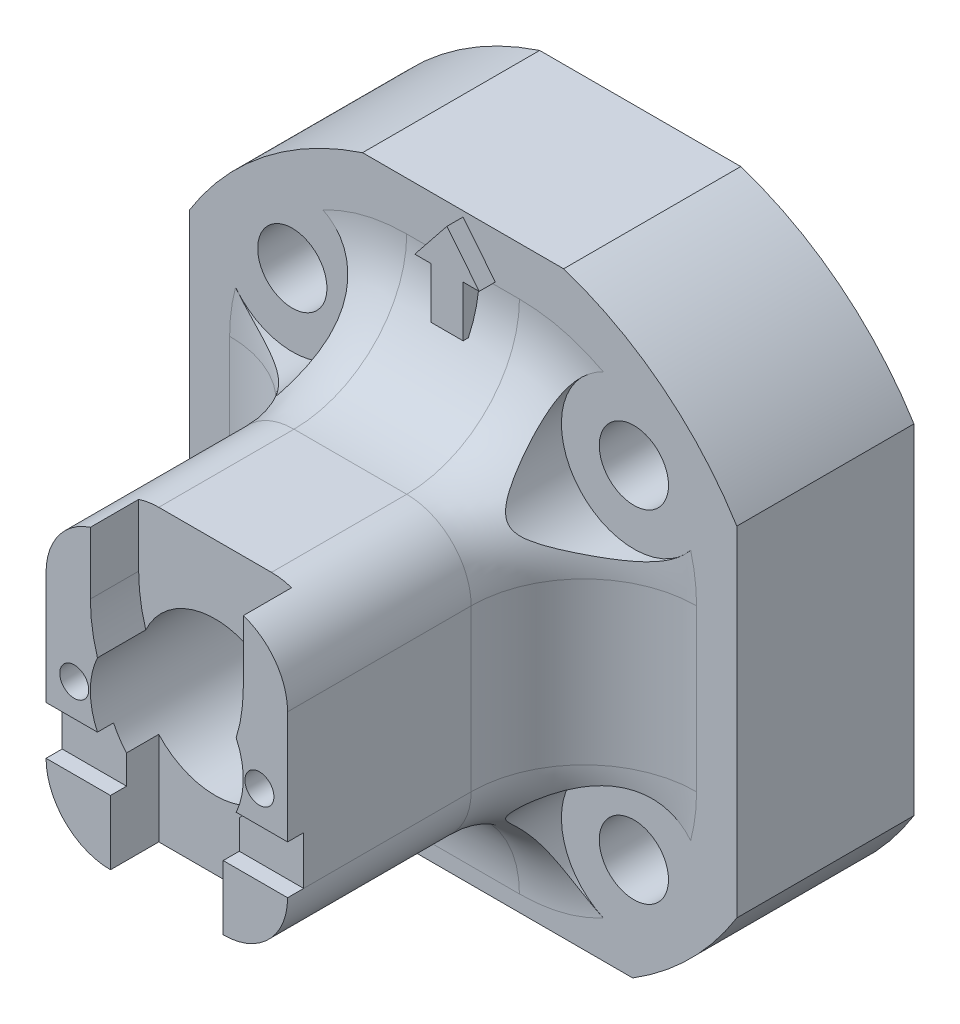
SolidWorks part; units mm, degrees
ref_plane "Front Plane" through (0, 0, 0) normal (0, 0, 1) x (1, 0, 0)
ref_plane "Top Plane" through (0, 0, 0) normal (0, 1, 0) x (1, 0, 0)
ref_plane "Right Plane" through (0, 0, 0) normal (1, 0, 0) x (0, 0, -1)
sketch "Sketch1" plane through (0, 0, 0) normal (0, 0, 1) x (1, 0, 0)
  circle A0 centre (0, 0) radius 20
  circle A1 centre (0, 0) radius 4.75
  dimension "D1" = 9.5
  dimension "D2" = 40
extrude "Boss-Extrude1" add sketch "Sketch1" along normal blind 11
sketch "Sketch2" plane through (0, 0, 11) normal (0, 0, 1) x (1, 0, 0)
  line L0 (0, 0) -> (0, 19) construction
  line L1 (-6.5933, 20) -> (6.5933, 20)
  line L2 (-6.5933, 20) -> (-6.5933, 19)
  line L3 (-6.5933, 19) -> (6.5933, 19)
  line L4 (6.5933, 20) -> (6.5933, 19)
  line L6 (-20, 15.8908) -> (-17, 15.8908)
  line L7 (-20, 15.8908) -> (-20, -10.5357)
  line L8 (-20, -10.5357) -> (-17, -10.5357)
  line L9 (-17, 15.8908) -> (-17, -10.5357)
  line L10 (20, 11.7256) -> (17, 11.7256)
  line L11 (20, 11.7256) -> (20, -14.8962)
  line L12 (20, -14.8962) -> (17, -14.8962)
  line L13 (17, 11.7256) -> (17, -14.8962)
  line L14 (19.7919, -20) -> (-18.9444, -20)
  line L15 (19.7919, -20) -> (19.7919, -17)
  line L16 (19.7919, -17) -> (-18.9444, -17)
  line L17 (-18.9444, -20) -> (-18.9444, -17)
  circle A0 centre (0, 0) radius 20 construction
  dimension "D1" = 1
  dimension "D2" = 3
extrude "Cut-Extrude1" cut sketch "Sketch2" against normal through all
sketch "Sketch3" plane through (0, 0, 11) normal (0, 0, 1) x (1, 0, 0)
  circle A0 centre (10.6066, -10.6066) radius 2 construction
  circle A1 centre (10.6066, 10.6066) radius 2 construction
  circle A2 centre (-10.6066, -10.6066) radius 2 construction
  circle A3 centre (-10.6066, 10.6066) radius 2 construction
  circle A4 centre (10.6066, -10.6066) radius 2 construction
  circle A5 centre (10.6066, 10.6066) radius 2 construction
  circle A6 centre (-10.6066, -10.6066) radius 2 construction
  circle A7 centre (-10.6066, 10.6066) radius 2 construction
  circle A8 centre (-10.6066, -10.6066) radius 2.15
  circle A9 centre (-10.6066, 10.6066) radius 2.15
  circle A10 centre (10.6066, 10.6066) radius 2.15
  circle A11 centre (10.6066, -10.6066) radius 2.15
  dimension "D1" = 4.3
extrude "Cut-Extrude2" cut sketch "Sketch3" against normal through all
sketch "Sketch5" plane through (0, 0, 11) normal (0, 0, 1) x (1, 0, 0)
  line L4 (7.5, -5) -> (7.5, 5)
  line L5 (3.5, 9) -> (-3.5, 9)
  line L6 (-7.5, 5) -> (-7.5, -5)
  line L7 (-3.5, -9) -> (3.5, -9)
  line L8 (7.5, -5) -> (7.5, 5)
  line L9 (3.5, 9) -> (-3.5, 9)
  line L10 (-7.5, 5) -> (-7.5, -5)
  line L11 (-3.5, -9) -> (3.5, -9)
  circle A0 centre (-5.75, 0) radius 1.075 construction
  circle A1 centre (5.75, 0) radius 1.075 construction
  circle A2 centre (-5.75, 0) radius 1.075 construction
  circle A3 centre (5.75, 0) radius 1.075 construction
  circle A4 centre (-5.75, 0) radius 0.9
  circle A5 centre (5.75, 0) radius 0.9
  arc A8 (3.5, -9) -> (7.5, -5) centre (3.5, -5) ccw
  arc A9 (7.5, 5) -> (3.5, 9) centre (3.5, 5) ccw
  arc A10 (-3.5, 9) -> (-7.5, 5) centre (-3.5, 5) ccw
  arc A11 (-7.5, -5) -> (-3.5, -9) centre (-3.5, -5) ccw
  arc A12 (3.5, -9) -> (7.5, -5) centre (3.5, -5) ccw
  arc A13 (7.5, 5) -> (3.5, 9) centre (3.5, 5) ccw
  arc A14 (-3.5, 9) -> (-7.5, 5) centre (-3.5, 5) ccw
  arc A15 (-7.5, -5) -> (-3.5, -9) centre (-3.5, -5) ccw
  dimension "D2" = 1.8
  dimension "D1" = 0
extrude "Boss-Extrude2" add sketch "Sketch5" along normal up to surface (18.4 mm away)
sketch "Sketch13" plane through (0, 0, 11) normal (0, 0, 1) x (1, 0, 0)
  circle A0 centre (5.75, 0) radius 0.9 construction
  circle A1 centre (-5.75, 0) radius 0.9 construction
  circle A2 centre (5.75, 0) radius 0.9
  circle A3 centre (-5.75, 0) radius 0.9
extrude "Boss-Extrude3" add sketch "Sketch13" along normal offset from surface (8.4 mm away) 10 up to face at (5.75, -0.9, 29.4)
sketch "Sketch7" plane through (0, 0, 29.4) normal (0, 0, 1) x (1, 0, 0)
  line L1 (-8.8438, -2) -> (9.3839, -2)
  line L2 (-8.8438, -2) -> (-8.8438, -5)
  line L3 (-8.8438, -5) -> (9.3839, -5)
  line L4 (9.3839, -2) -> (9.3839, -5)
  dimension "D1" = 3
  dimension "D2" = 2
extrude "Cut-Extrude4" cut sketch "Sketch7" against normal blind 1
fillet "Fillet1" radius 7 8 edges at (-6.3284, 7.8284, 11) (0, 9, 11) (6.3284, 7.8284, 11) (7.5, 0, 11) (6.3284, -7.8284, 11) (0, -9, 11) (-6.3284, -7.8284, 11) (-7.5, 0, 11)
sketch "Sketch9" plane through (0, 0, 11) normal (0, 0, 1) x (1, 0, 0)
  circle A7 centre (10.6066, 10.6066) radius 2 construction
  circle A9 centre (-10.6066, 10.6066) radius 2 construction
  circle A11 centre (-10.6066, -10.6066) radius 2 construction
  circle A13 centre (10.6066, -10.6066) radius 2 construction
  circle A14 centre (10.6066, 10.6066) radius 4.5
  circle A15 centre (10.6066, -10.6066) radius 4.5
  circle A16 centre (-10.6066, -10.6066) radius 4.5
  circle A17 centre (-10.6066, 10.6066) radius 4.5
  arc A18 (-12.7206, 10.9984) -> (-11.4796, 12.5714) centre (-10.6066, 10.6066) ccw construction
  arc A19 (11.4796, 12.5714) -> (12.7206, 10.9984) centre (10.6066, 10.6066) ccw construction
  arc A20 (12.7206, -10.9984) -> (11.4796, -12.5714) centre (10.6066, -10.6066) ccw construction
  arc A21 (-11.4796, -12.5714) -> (-12.7206, -10.9984) centre (-10.6066, -10.6066) ccw construction
  dimension "D1" = 9
extrude "Cut-Extrude5" cut sketch "Sketch9" along normal through all
sketch "Sketch10" plane through (0, 0, 0) normal (0, 0, -1) x (-1, 0, 0)
  circle A0 centre (0, 0) radius 4.75 construction
  circle A1 centre (0, 0) radius 4.75
extrude "Cut-Extrude6" cut sketch "Sketch10" against normal through all
sketch "Sketch11" plane through (0, 9, 0) normal (0, 1, 0) x (1, 0, 0)
  line L1 (-4.75, -29.4) -> (4.75, -29.4)
  line L2 (-4.75, -29.4) -> (-4.75, -26.4)
  line L3 (-4.75, -26.4) -> (4.75, -26.4)
  line L4 (4.75, -29.4) -> (4.75, -26.4)
  line L5 (0, 0) -> (0, -26.4) construction
  line L6 (-6.245, 0) -> (6.245, 0) construction
  point P7 (0, 0)
  point P8 (0, 0)
  dimension "D1" = 3
  dimension "D2" = 9.5
extrude "Cut-Extrude7" cut sketch "Sketch11" against normal blind 7
sketch "Sketch12" plane through (0, 0, 0) normal (0, 0, -1) x (-1, 0, 0)
  circle A0 centre (0, 0) radius 6
  dimension "D1" = 12
extrude "Cut-Extrude8" cut sketch "Sketch12" against normal offset from surface (14.4 mm away) 15 up to face at (-5.6956, 2.3742, 29.4)
chamfer "Chamfer2" distance 1.5 angle 45 1 edges at (0, -6, 14.4)
chamfer "Chamfer1" distance 4 angle 50 1 edges at (-6, 0, 0) first distance on face at (-6, 0, 0)
fillet "Fillet2" radius 10 2 edges at (4.75, 2, 27.9) (-4.75, 2, 27.9)
sketch "Sketch14" plane through (0, -9, 0) normal (0, -1, 0) x (1, 0, 0)
  line L0 (3.5, 29.4) -> (3.5, 18) construction
  line L1 (-3.5, 29.4) -> (3.5, 29.4)
  line L2 (-3.5, 29.4) -> (-3.5, 26.4)
  line L3 (-3.5, 26.4) -> (3.5, 26.4)
  line L4 (3.5, 29.4) -> (3.5, 26.4)
  line L5 (3.5, 26.4) -> (-3.5, 26.4) construction
extrude "Cut-Extrude9" cut sketch "Sketch14" against normal blind 10
sketch "Sketch15" plane through (0, 0, 11) normal (0, 0, 1) x (1, 0, 0)
  line L0 (-1, 13.002) -> (1, 13.002)
  line L1 (1, 13.002) -> (1, 16.1642)
  line L2 (1, 16.1642) -> (2, 16.1642)
  line L3 (2, 16.1642) -> (0, 18.6642)
  line L4 (0, 18.6642) -> (-2, 16.1642)
  line L5 (-2, 16.1642) -> (-1, 16.1642)
  line L6 (-1, 16.1642) -> (-1, 13.002)
  line L7 (0, 0) -> (0, 13.002) construction
  point P10 (0, 18.7096)
  point P11 (0, 18.6642)
  dimension "D1" = 2
  dimension "D2" = 4
  dimension "D3" = 2.5
extrude "Boss-Extrude4" add sketch "Sketch15" along normal blind 1
